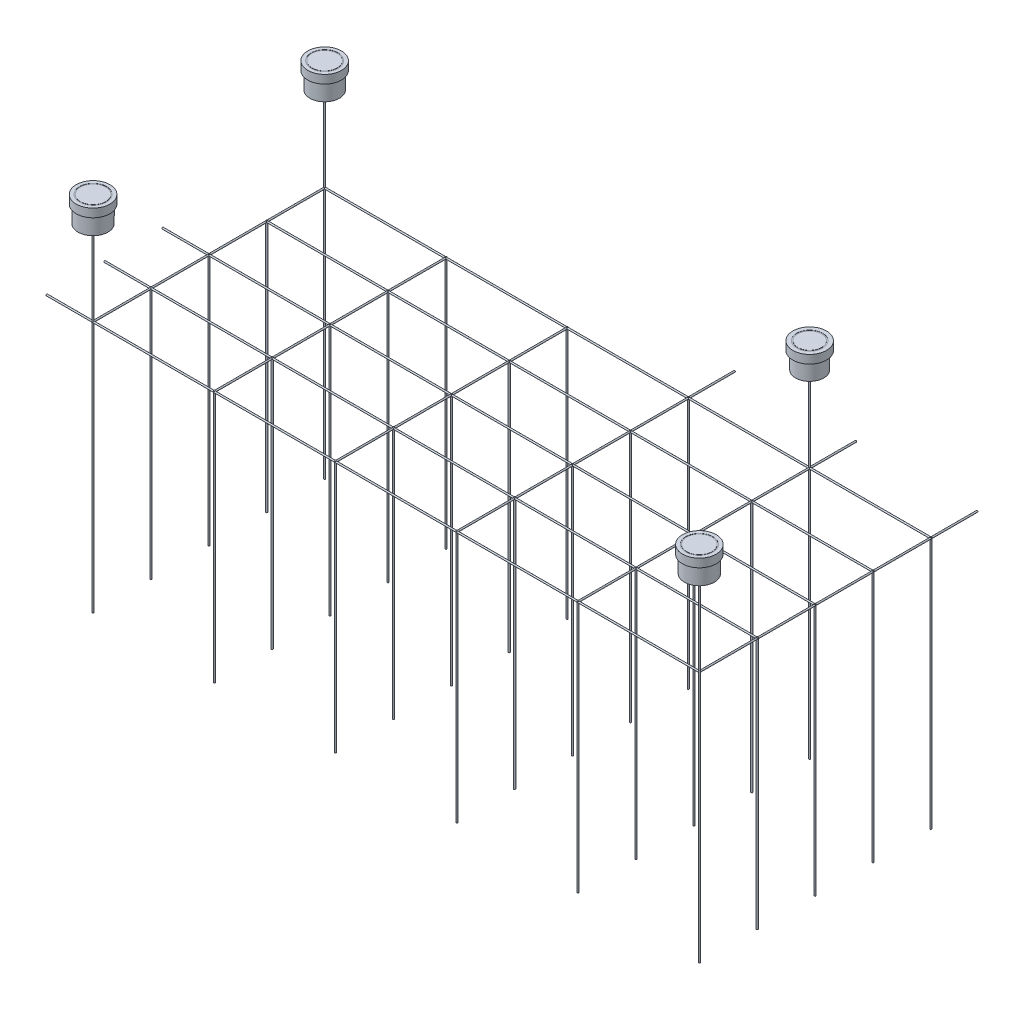
SolidWorks part; units mm, degrees
ref_plane "Alzado" through (0, 0, 0) normal (0, 0, 1) x (1, 0, 0)
ref_plane "Planta" through (0, 0, 0) normal (0, 1, 0) x (1, 0, 0)
ref_plane "Vista lateral" through (0, 0, 0) normal (1, 0, 0) x (0, 0, -1)
sketch "Croquis1" plane through (0, 0, 0) normal (0, 1, 0) x (1, 0, 0)
  line L0 (-3600, 1375) -> (-2160, 1375) construction
  line L1 (-3600, -1375) -> (-2160, -1375) construction
  line L7 (-3600, -1375) -> (3600, -1375) construction
  line L8 (-3600, -1375) -> (-3600, 1375) construction
  line L9 (-3600, 1375) -> (3600, 1375) construction
  line L10 (3600, -1375) -> (3600, 1375) construction
  line L11 (-3600, -1375) -> (3600, 1375) construction
  line L12 (-3600, 1375) -> (3600, -1375) construction
  circle A0 centre (-3600, 1375) radius 9
  circle A1 centre (-2160, 1375) radius 9
  circle A2 centre (-720, 1375) radius 9
  circle A3 centre (720, 1375) radius 9
  circle A4 centre (2160, 1375) radius 9
  circle A5 centre (3600, 1375) radius 9
  circle A6 centre (-3600, -1375) radius 9
  circle A7 centre (-2160, -1375) radius 9
  circle A8 centre (-720, -1375) radius 9
  circle A9 centre (720, -1375) radius 9
  circle A10 centre (2160, -1375) radius 9
  circle A11 centre (3600, -1375) radius 9
  point P0 (0, 0)
  point P6 (0, 0)
  dimension "D1" = 18
  dimension "D6" = 18
  dimension "D2" = 6
  dimension "D3" = 7200
  dimension "D4" = 2750
  dimension "D5" = 1440
  dimension "D8" = 1440
  dimension "D7" = 6
extrude "Saliente-Extruir1" add sketch "Croquis1" against normal blind 3000
sketch "Croquis2" plane through (0, 0, 0) normal (0, 1, 0) x (1, 0, 0)
  circle A0 centre (-3600, 1375) radius 9
extrude "Saliente-Extruir2" add sketch "Croquis2" against normal blind 3000
pattern_linear "MatrizL2" count 4 spacing 687.5 along (0, 0, 1) of "Saliente-Extruir2"
sketch "Croquis3" plane through (0, 0, 0) normal (0, 1, 0) x (1, 0, 0)
  circle A0 centre (-3600, -687.5) radius 9
  circle A1 centre (-3600, 0) radius 9
  circle A2 centre (-3600, 687.5) radius 9
extrude "Saliente-Extruir3" add sketch "Croquis3" against normal blind 3000
pattern_linear "MatrizL4" count 6 spacing 1440 along (1, 0, 0) of "Saliente-Extruir3"
sketch "Croquis4" plane through (0, 0, 0) normal (1, 0, 0) x (0, 0, -1)
  line L0 (1375, 0) -> (1375, -9) construction
  line L1 (1384, 0) -> (1366, 0) construction
  circle A0 centre (1375, -9) radius 9
  dimension "D1" = 9
extrude "Saliente-Extruir4" add sketch "Croquis4" along normal blind 3600 and the other way blind 3600
sketch "Croquis5" plane through (0, 0, 0) normal (1, 0, 0) x (0, 0, -1)
  line L0 (1375, 0) -> (1375, -9) construction
  line L1 (1375, -9) -> (-1384, -9) construction
  line L2 (-1384, 0) -> (-1384, -3000) construction
  line L3 (687.5, 0) -> (687.5, -9) construction
  line L4 (696.5, 0) -> (678.5, 0) construction
  line L5 (0, 0) -> (0, -9) construction
  line L6 (-687.5, 0) -> (-687.5, -9) construction
  line L7 (-678.5, 0) -> (-696.5, 0) construction
  line L8 (-1375, 0) -> (-1375, -9) construction
  line L9 (-1366, 0) -> (-1384, 0) construction
  circle A0 centre (687.5, -9) radius 9
  circle A1 centre (0, -9) radius 9
  circle A2 centre (-687.5, -9) radius 9
  circle A3 centre (-1375, -9) radius 9
  dimension "D1" = 9
extrude "Saliente-Extruir5" add sketch "Croquis5" along normal blind 3600 and the other way blind 3600
sketch "Croquis6" plane through (0, 0, 0) normal (0, 0, 1) x (1, 0, 0)
  line L0 (3600, 0) -> (3600, -9) construction
  line L1 (3609, 0) -> (3591, 0) construction
  line L2 (3600, -9) -> (3591, 0) construction
  line L3 (3600, -9) -> (3591, -18) construction
  line L4 (3600, -9) -> (-3600, -9) construction
  line L5 (-3591, 0) -> (-3600, -9) construction
  line L6 (-3591, -18) -> (-3600, -9) construction
  circle A0 centre (-3600, -9) radius 9
  circle A1 centre (-2160, -9) radius 9
  circle A2 centre (-720, -9) radius 9
  circle A3 centre (720, -9) radius 9
  circle A4 centre (2160, -9) radius 9
  circle A5 centre (3600, -9) radius 9
extrude "Saliente-Extruir6" add sketch "Croquis6" along normal blind 1375 and the other way blind 1375
sketch "Croquis7" plane through (0, 0, 0) normal (0, 1, 0) x (1, 0, 0)
  circle A0 centre (3600, -1375) radius 9
extrude "Saliente-Extruir7" add sketch "Croquis7" along normal blind 1300
sketch "Croquis8" plane through (0, 1300, 0) normal (0, 1, 0) x (1, 0, 0)
  circle A0 centre (3600, -1375) radius 200
  dimension "D1" = 400
extrude "Saliente-Extruir8" add sketch "Croquis8" against normal blind 100
sketch "Croquis9" plane through (0, 1300, 0) normal (0, 1, 0) x (1, 0, 0)
  circle A0 centre (3600, -1375) radius 160
  circle A1 centre (3600, -1375) radius 150
  dimension "D1" = 320
  dimension "D2" = 10
extrude "Cortar-Extruir1" cut sketch "Croquis9" against normal blind 2
sketch "Croquis10" plane through (0, 1200, 0) normal (0, -1, 0) x (1, 0, 0)
  circle A0 centre (3600, 1375) radius 178.0393
extrude "Saliente-Extruir9" add sketch "Croquis10" along normal blind 200
pattern_linear "MatrizL6" count 2 spacing 7200 along (-1, 0, 0) of "Saliente-Extruir7", "Saliente-Extruir8", "Cortar-Extruir1", "Saliente-Extruir9"
sketch "Croquis12" plane through (0, 0, 0) normal (0, 1, 0) x (1, 0, 0)
  circle A0 centre (-3600, 1375) radius 9
extrude "Saliente-Extruir11" add sketch "Croquis12" along normal blind 1300
sketch "Croquis13" plane through (0, 1300, 0) normal (0, 1, 0) x (1, 0, 0)
  circle A0 centre (-3600, 1375) radius 200
  dimension "D1" = 400
extrude "Saliente-Extruir12" add sketch "Croquis13" against normal blind 100
sketch "Croquis14" plane through (0, 1200, 0) normal (0, -1, 0) x (1, 0, 0)
  circle A0 centre (-3600, -1375) radius 175
  dimension "D1" = 350
extrude "Saliente-Extruir13" add sketch "Croquis14" along normal blind 200
sketch "Croquis15" plane through (0, 1300, 0) normal (0, 1, 0) x (1, 0, 0)
  circle A0 centre (-3600, 1375) radius 150
  circle A1 centre (-3600, 1375) radius 160
  dimension "D1" = 320
  dimension "D2" = 10
extrude "Cortar-Extruir2" cut sketch "Croquis15" against normal blind 2
ref_plane "Plano1" through (0, 0, 0) normal (0, 0, 1) x (1, 0, 0)
ref_plane "Plano2" through (0, 0, 0) normal (1, 0, 0) x (0, 0, -1)
sketch "Croquis16" plane through (0, 0, 0) normal (0, 1, 0) x (1, 0, 0)
  circle A0 centre (3600, 687.5) radius 9
sketch "Croquis25" plane through (0, 0, 0) normal (0, 1, 0) x (1, 0, 0)
  line L0 (3609, 1375) -> (3591, 1375) construction
  arc A0 (3600, 1366) -> (3591, 1375) centre (3600, 1375) ccw construction
ref_plane "Plano4" through (0, 0, -1375) normal (0, 0, -1) x (-1, 0, 0)
sketch "Croquis26" plane through (0, 0, -1375) normal (0, 0, -1) x (-1, 0, 0)
  circle A0 centre (-3600, -9) radius 9
  dimension "D1" = 18
extrude "Saliente-Extruir18" add sketch "Croquis26" along normal blind 550
sketch "Croquis27" plane through (0, 1300, 0) normal (0, 1, 0) x (1, 0, 0)
  line L0 (-3600, -1225) -> (-3600, -1525) construction
  circle A0 centre (-3600, -1375) radius 150 construction
  circle A1 centre (-3600, -1375) radius 150 construction
ref_plane "Plano5" through (-3600, 0, 0) normal (-1, 0, 0) x (0, 0, 1)
sketch "Croquis28" plane through (-3600, 0, 0) normal (-1, 0, 0) x (0, 0, 1)
  circle A0 centre (1375, -9) radius 9
extrude "Saliente-Extruir19" add sketch "Croquis28" along normal blind 550
pattern_linear "MatrizL7" count 3 spacing 687.5 along (0, 0, -1) of "Saliente-Extruir19"
pattern_linear "MatrizL8" count 3 spacing 1440 along (-1, 0, 0) of "Saliente-Extruir18"
sketch "Croquis29" plane through (0, 0, 0) normal (0, 1, 0) x (1, 0, 0)
  circle A0 centre (2160, 1375) radius 9
extrude "Saliente-Extruir20" add sketch "Croquis29" along normal blind 1300
sketch "Croquis30" plane through (0, 1300, 0) normal (0, 1, 0) x (1, 0, 0)
  line L0 (2169, 1375) -> (2160, 1375) construction
  line L1 (2160, 1375) -> (2160, 1366) construction
  circle A0 centre (2160, 1375) radius 9 construction
  circle A1 centre (2160, 1375) radius 200
  dimension "D1" = 400
extrude "Saliente-Extruir21" add sketch "Croquis30" against normal blind 100
sketch "Croquis31" plane through (0, 1200, 0) normal (0, -1, 0) x (1, 0, 0)
  circle A0 centre (2160, -1375) radius 167.9119
extrude "Saliente-Extruir22" add sketch "Croquis31" along normal blind 200
sketch "Croquis32" plane through (0, 1300, 0) normal (0, 1, 0) x (1, 0, 0)
  circle A0 centre (2160, 1375) radius 154.1425
  circle A1 centre (2160, 1375) radius 141.004
extrude "Cortar-Extruir4" cut sketch "Croquis32" against normal blind 2
